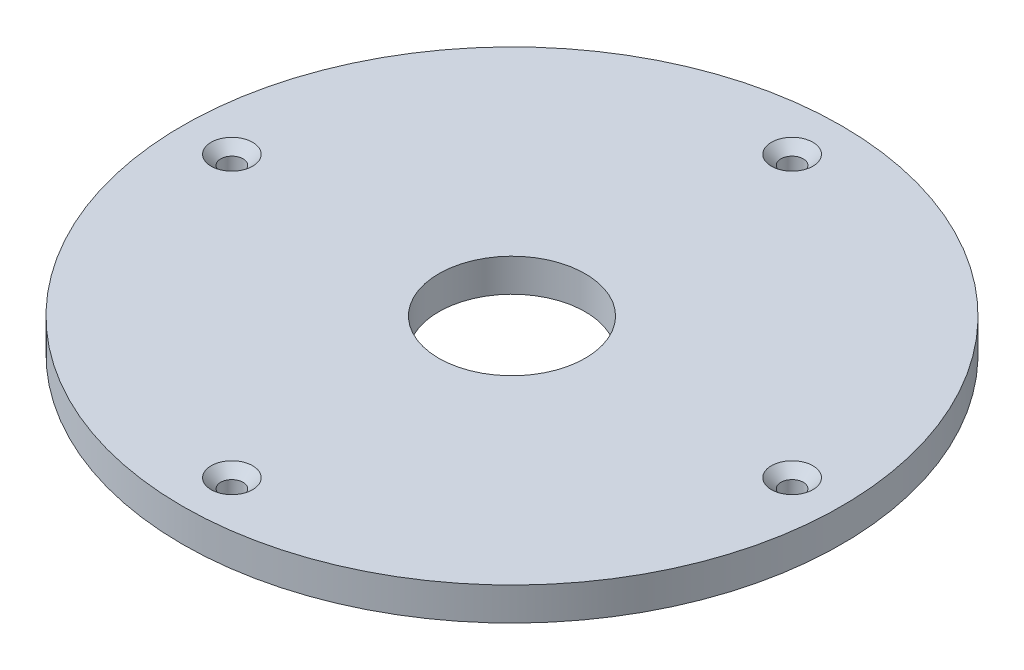
SolidWorks part; units mm, degrees
ref_plane "Front Plane" through (0, 0, 0) normal (0, 0, 1) x (1, 0, 0)
ref_plane "Top Plane" through (0, 0, 0) normal (0, 1, 0) x (1, 0, 0)
ref_plane "Right Plane" through (0, 0, 0) normal (1, 0, 0) x (0, 0, -1)
sketch "Sketch1" plane through (0, 0, 0) normal (0, 1, 0) x (1, 0, 0)
  circle A0 centre (0, 0) radius 50
  circle A1 centre (0, 0) radius 11.1125
  point P0 (0, 42.5)
  point P5 (16.8071, 39.0355)
  point P6 (0, 0)
  dimension "D2" = 22.225
  dimension "D3" = 100
  dimension "D1" = 42.5
extrude "Boss-Extrude1" add sketch "Sketch1" along normal blind 5
sketch "Sketch2" plane through (0, 5, 0) normal (0, 1, 0) x (1, 0, 0)
  point P0 (0, 42.5)
hole_wizard "CSK for M3 Flat Head Machine Screw1" positions "Sketch2" profile "Sketch3" countersink size "M3" standard "ANSI Metric" end condition up to next
sketch "Sketch3" plane through (0, 5, -42.5) normal (1, 0, 0) x (0, 0, 1)
  line L0 (0, 0) -> (0, 5)
  line L1 (0, 5) -> (1.7, 5)
  line L2 (1.7, 5) -> (1.7, 1.45)
  line L3 (1.7, 1.45) -> (3.15, 0)
  line L5 (3.15, 0) -> (0, 0)
  line L6 (-1.7, 1.45) -> (-3.15, 0) construction
  line L11 (0, -6.35) -> (0, 107.95) construction
  dimension "Thru Hole Dia." = 3.4
  dimension "Thru Hole Depth" = 5
  dimension "Near C'Sink Dia." = 6.3
  dimension "Near C'Sink Angle" = 90
pattern_circular "CirPattern1" count 4 every 90 about axis through (0, 5, 0) along (0, -1, 0) of "CSK for M3 Flat Head Machine Screw1"
chamfer "Chamfer1" [suppressed] distance 2 angle 45
